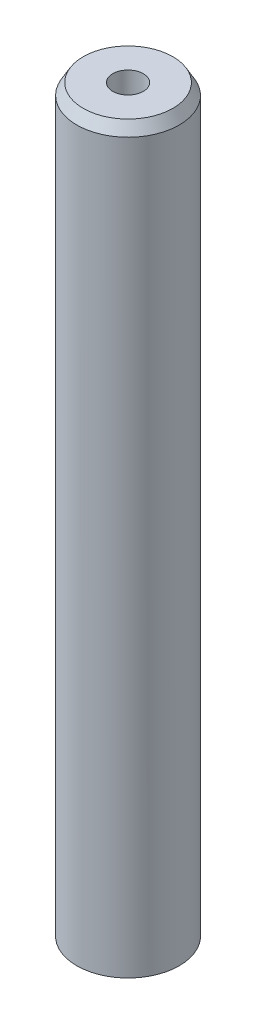
SolidWorks part; units mm, degrees
ref_plane "Front Plane" through (0, 0, 0) normal (0, 0, 1) x (1, 0, 0)
ref_plane "Top Plane" through (0, 0, 0) normal (0, 1, 0) x (1, 0, 0)
ref_plane "Right Plane" through (0, 0, 0) normal (1, 0, 0) x (0, 0, -1)
sketch "Sketch1" plane through (0, 0, 0) normal (0, 1, 0) x (1, 0, 0)
  circle A0 centre (0, 0) radius 12.5
  dimension "SHAFT_OD" = 25
extrude "Boss-Extrude1" add sketch "Sketch1" along normal blind 181.8785
sketch "Sketch2" plane through (0, 0, 0) normal (0, 1, 0) x (1, 0, 0)
  circle A0 centre (0, 0) radius 3.7371
  dimension "BORE_D" = 7.4742
extrude "Cut-Extrude1" cut sketch "Sketch2" along normal through all
chamfer "Chamfer1" distance 2.7256 angle 30 2 edges at (0, 181.8785, 12.5) (0, 0, 12.5) first distance on face at (0, 181.8785, 12.5) first distance on face at (0, 0, 3.7371)
